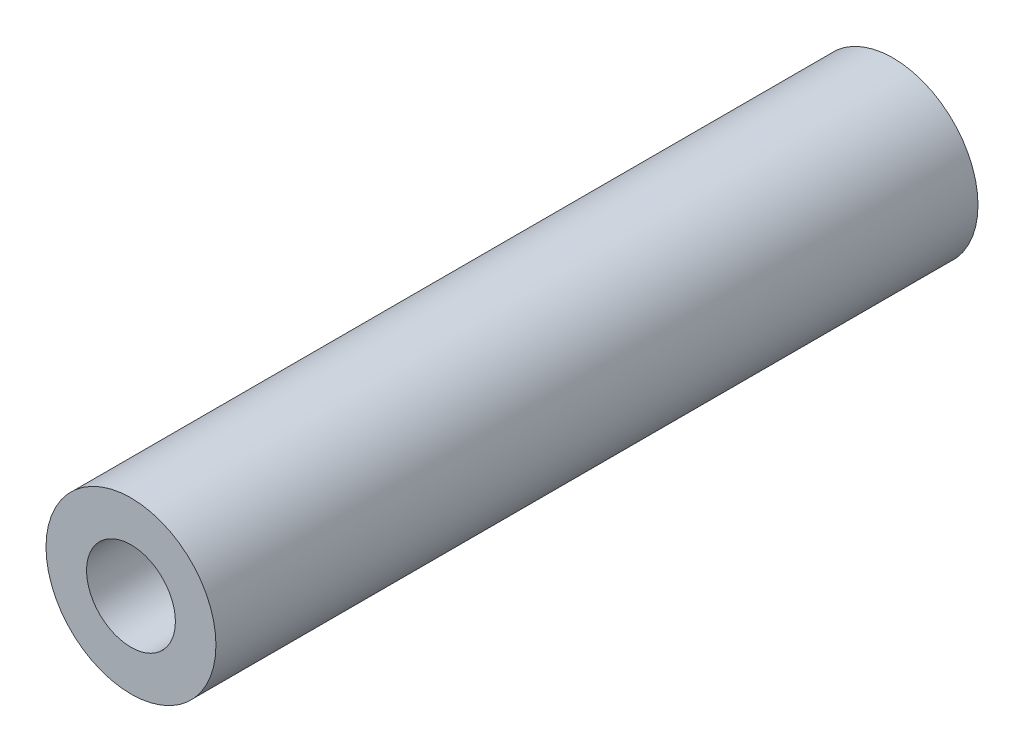
SolidWorks part; units mm, degrees
ref_plane "Front Plane" through (0, 0, 0) normal (0, 0, 1) x (1, 0, 0)
ref_plane "Top Plane" through (0, 0, 0) normal (0, 1, 0) x (1, 0, 0)
ref_plane "Right Plane" through (0, 0, 0) normal (1, 0, 0) x (0, 0, -1)
sketch "Sketch1" plane through (0, 0, 0) normal (0, 0, 1) x (1, 0, 0)
  circle A0 centre (0, 0) radius 2.4892
  circle A1 centre (0, 0) radius 4.7625
  dimension "D1" = 4.9784
  dimension "D2" = 9.525
extrude "Boss-Extrude1" add sketch "Sketch1" along normal mid plane 42.7101 contours A0 | A1 region at (0, 0, 0)
